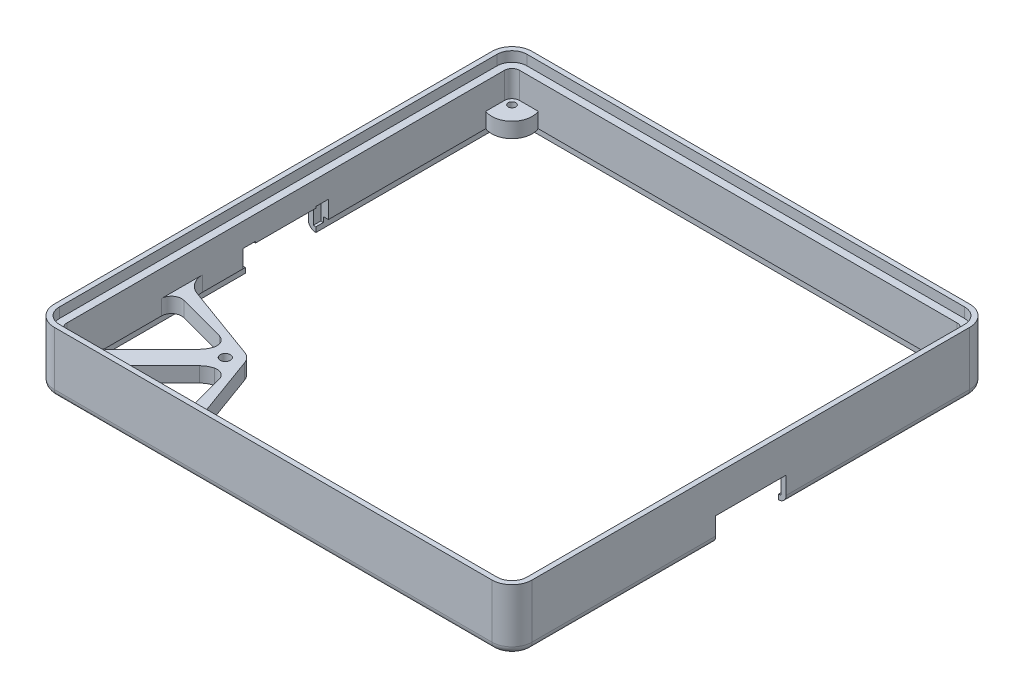
SolidWorks part; units mm, degrees
ref_plane "Front Plane" through (0, 0, 0) normal (0, 0, 1) x (1, 0, 0)
ref_plane "Top Plane" through (0, 0, 0) normal (0, 1, 0) x (1, 0, 0)
ref_plane "Right Plane" through (0, 0, 0) normal (1, 0, 0) x (0, 0, -1)
sketch "Sketch2" plane through (0, 0, 0) normal (0, 1, 0) x (1, 0, 0)
  line L1 (-43.5, -47.5) -> (43.5, -47.5)
  line L2 (-47.5, -43.5) -> (-47.5, 43.5)
  line L3 (-43.5, 47.5) -> (43.5, 47.5)
  line L4 (47.5, -43.5) -> (47.5, 43.5)
  line L5 (-43.5, -43.5) -> (43.5, 43.5) construction
  line L6 (-43.5, 43.5) -> (43.5, -43.5) construction
  arc A0 (-43.5, -47.5) -> (-47.5, -43.5) centre (-43.5, -43.5) cw
  arc A1 (43.5, -47.5) -> (47.5, -43.5) centre (43.5, -43.5) ccw
  arc A2 (43.5, 47.5) -> (47.5, 43.5) centre (43.5, 43.5) cw
  arc A3 (-47.5, 43.5) -> (-43.5, 47.5) centre (-43.5, 43.5) cw
  point P0 (0, 0)
  dimension "D1" = 4
  dimension "D2" = 95
sketch "Sketch3" plane through (0, 0, 0) normal (0, 0, 1) x (1, 0, 0)
  line L0 (0, 0) -> (0, -1.6)
  line L1 (-43.5, 0) -> (43.5, 0) construction
  line L2 (0, -1.6) -> (0, -8.5)
  line L3 (0, -8.5) -> (0, -10)
  dimension "D1" = 1.6
  dimension "D2" = 10
  dimension "D3" = 1.5
extrude "Boss-Extrude1" add sketch "Sketch2" against normal up to vertex (10 mm away) and the other way blind 2.2 up to point (0, -10, 0)
shell "Shell1" thickness 2.5 removed face at (0, -10, 0) removed face at (0, 2.2, 0)
sketch "Sketch4" plane through (0, 0, 0) normal (0, 1, 0) x (1, 0, 0)
  line L19 (-46.5, 43.5) -> (-46.5, -43.5)
  line L20 (-43.5, -46.5) -> (43.5, -46.5)
  line L21 (46.5, -43.5) -> (46.5, 43.5)
  line L22 (43.5, 46.5) -> (-43.5, 46.5)
  line L23 (-46.5, 43.5) -> (-46.5, -43.5)
  line L24 (-43.5, -46.5) -> (43.5, -46.5)
  line L25 (46.5, -43.5) -> (46.5, 43.5)
  line L26 (43.5, 46.5) -> (-43.5, 46.5)
  arc A16 (-46.5, -43.5) -> (-43.5, -46.5) centre (-43.5, -43.5) ccw
  arc A17 (43.5, -46.5) -> (46.5, -43.5) centre (43.5, -43.5) ccw
  arc A18 (46.5, 43.5) -> (43.5, 46.5) centre (43.5, 43.5) ccw
  arc A19 (-43.5, 46.5) -> (-46.5, 43.5) centre (-43.5, 43.5) ccw
  arc A20 (-46.5, -43.5) -> (-43.5, -46.5) centre (-43.5, -43.5) ccw
  arc A21 (43.5, -46.5) -> (46.5, -43.5) centre (43.5, -43.5) ccw
  arc A22 (46.5, 43.5) -> (43.5, 46.5) centre (43.5, 43.5) ccw
  arc A23 (-43.5, 46.5) -> (-46.5, 43.5) centre (-43.5, 43.5) ccw
  dimension "D1" = 1
extrude "Topplate cutout" cut sketch "Sketch4" along normal through all from offset 0.2
fillet "Fillet1" radius 1.5 8 edges at (-46.3284, -10, 46.3284) (-47.5, -10, 0) (-46.3284, -10, -46.3284) (0, -10, -47.5) (46.3284, -10, -46.3284) (47.5, -10, 0) (46.3284, -10, 46.3284) (0, -10, 47.5)
sketch "Sketch5" plane through (0, 0, 0) normal (1, 0, 0) x (0, 0, -1)
  line L0 (-8.5, -4.5) -> (-6, -4.5)
  line L1 (-7, -5) -> (7, -5)
  line L2 (-7, -5) -> (-7, -10)
  line L3 (-7, -10) -> (7, -10)
  line L4 (7, -5) -> (7, -10)
  line L5 (0, -8.5) -> (0, -10) construction
  line L6 (0, -8.5) -> (0, -10) construction
  line L7 (-6, -4.5) -> (-6, -4.8)
  line L8 (-6, -4.8) -> (6, -4.8)
  line L9 (6, -4.8) -> (6, -4.5)
  line L10 (6, -4.5) -> (8.5, -4.5)
  line L11 (-7, -9) -> (-8.5, -9)
  line L13 (-8.5, -9) -> (-8.5, -4.5)
  line L14 (8.5, -4.5) -> (8.5, -9)
  line L15 (8.5, -9) -> (7, -9)
  dimension "D1" = 14
  dimension "D2" = 5
  dimension "D3" = 1
  dimension "D4" = 17
  dimension "D5" = 12
  dimension "D6" = 0.2
  dimension "D7" = 0.5
extrude "connector cutout" cut sketch "Sketch5" against normal through all both and the other way through all contours L4 L1 L2 L3 region at (0, -7.5, 0)
ref_plane "Plane1" through (0, -10, 0) normal (0, 1, 0) x (1, 0, 0)
sketch "Sketch6" plane through (0, -10, 0) normal (0, 1, 0) x (1, 0, 0)
  line L0 (-41, 0) -> (0, 0) construction
  line L1 (-43.5, -43.5) -> (43.5, 43.5) construction
  line L2 (-46, -7) -> (-46, -43.5)
  line L3 (0, 0) -> (0, -32.2074) construction
  line L4 (-46, 7) -> (-41, 7)
  line L5 (-41, 7) -> (-41, -7)
  line L6 (-41, -7) -> (-46, -7)
  line L7 (41, -7) -> (46, -7)
  line L8 (-43.5, -46) -> (43.5, -46)
  line L9 (46, -43.5) -> (46, 43.5)
  line L10 (43.5, 46) -> (-43.5, 46)
  line L11 (-46, 43.5) -> (-46, -43.5)
  line L12 (-43.5, -46) -> (43.5, -46)
  line L13 (46, -43.5) -> (46, -7)
  line L14 (43.5, 46) -> (-43.5, 46)
  line L15 (-46, 43.5) -> (-46, 7)
  line L16 (41, 7) -> (41, -7)
  line L17 (46, 7) -> (41, 7)
  line L18 (46, 7) -> (46, 43.5)
  arc A8 (43.5, -46) -> (46, -43.5) centre (43.5, -43.5) ccw
  arc A9 (46, 43.5) -> (43.5, 46) centre (43.5, 43.5) ccw
  arc A10 (-43.5, 46) -> (-46, 43.5) centre (-43.5, 43.5) ccw
  arc A11 (-46, -43.5) -> (-43.5, -46) centre (-43.5, -43.5) ccw
  arc A12 (43.5, -46) -> (46, -43.5) centre (43.5, -43.5) ccw
  arc A13 (46, 43.5) -> (43.5, 46) centre (43.5, 43.5) ccw
  arc A14 (-43.5, 46) -> (-46, 43.5) centre (-43.5, 43.5) ccw
  arc A15 (-46, -43.5) -> (-43.5, -46) centre (-43.5, -43.5) ccw
  dimension "D2" = 14
  dimension "D3" = 5
  dimension "D1" = 1.5
extrude "Cut-Extrude1" cut sketch "Sketch6" along normal blind 2 contours L2 A15 L12 A12 L13 L7 L16 L17 L18 A13 L14 A14 L15 L4 L5 L6 | L12 A12 L13 L7 L16 L17 L18 A13 L14 A14 L15 L4 L5 L6 L2 A15 region at (0, -10, 0)
extrude "Cut-Extrude2" cut sketch "Sketch5<3>" along normal offset from surface 1 and the other way offset from surface 1 contours L15 L14 L10 L9 L8 L7 L0 L13 L11 L2 L1 L4 region at (0, -4.6759, 7.25) up to face at (47.5, -4.95, 0) other way up to face at (-47.5, -4.95, 0)
sketch "Sketch5<3>" plane through (0, 0, 0) normal (1, 0, 0) x (0, 0, -1) same geometry as "Sketch5"
sketch "Sketch8" plane through (0, -8, 0) normal (0, -1, 0) x (1, 0, 0)
  line L0 (-43.5, 43.5) -> (43.5, -43.5) construction
  line L1 (-43.5, -43.5) -> (43.5, 43.5) construction
  line L2 (-25.6809, 27.4739) -> (-20.2599, 42.3681)
  line L3 (-43.5, 45) -> (43.5, 45) construction
  line L5 (-39.0377, 41.8662) -> (-29.6353, 32.4637)
  line L6 (-25.3588, 32.8339) -> (-22.7735, 42.4824)
  line L8 (-43.5, 43.5) -> (43.5, -43.5) construction
  line L9 (-16.5011, 45) -> (-24.7053, 45)
  line L10 (-37.5209, 45) -> (-39.7919, 45)
  line L11 (-27.4739, 25.6809) -> (-42.3681, 20.2599)
  line L12 (-45, 16.5011) -> (-45, 24.7053)
  line L13 (-32.8339, 25.3588) -> (-42.4824, 22.7735)
  line L14 (-41.8662, 39.0377) -> (-32.4637, 29.6353)
  line L15 (-45, 37.5209) -> (-45, 39.7919)
  circle A0 centre (-43.5, 43.5) radius 4
  circle A1 centre (43.5, 43.5) radius 4
  circle A2 centre (43.5, -43.5) radius 4
  circle A3 centre (-43.5, -43.5) radius 4
  circle A4 centre (-43.5, 43.5) radius 0.75
  circle A5 centre (43.5, 43.5) radius 0.75
  circle A6 centre (-43.5, -43.5) radius 0.75
  circle A7 centre (43.5, -43.5) radius 0.75
  circle A8 centre (-28.5, 28.5) radius 1
  circle A9 centre (28.5, 28.5) radius 1
  circle A10 centre (-28.5, -28.5) radius 1
  circle A11 centre (28.5, -28.5) radius 1
  circle A12 centre (-28.5, 28.5) radius 3
  circle A13 centre (28.5, 28.5) radius 3
  circle A14 centre (28.5, -28.5) radius 3
  circle A15 centre (-28.5, -28.5) radius 3
  arc A16 (-20.2599, 42.3681) -> (-16.5011, 45) centre (-16.5011, 41) cw
  arc A17 (-39.5139, 43.1667) -> (-37.5209, 45) centre (-37.5209, 43) cw
  arc A18 (-39.5139, 43.1667) -> (-39.0377, 41.8662) centre (-37.8744, 43.0296) ccw
  arc A19 (-29.6353, 32.4637) -> (-27.7744, 31.4109) centre (-26.8069, 35.2922) ccw
  arc A20 (-27.7744, 31.4109) -> (-25.3588, 32.8339) centre (-27.2906, 33.3515) ccw
  arc A21 (-22.7735, 42.4824) -> (-24.7053, 45) centre (-24.7053, 43) ccw
  arc A22 (-42.3681, 20.2599) -> (-45, 16.5011) centre (-41, 16.5011) ccw
  arc A23 (-42.4824, 22.7735) -> (-45, 24.7053) centre (-43, 24.7053) cw
  arc A24 (-31.4109, 27.7744) -> (-32.8339, 25.3588) centre (-33.3515, 27.2906) cw
  arc A25 (-32.4637, 29.6353) -> (-31.4109, 27.7744) centre (-35.2922, 26.8069) cw
  arc A26 (-43.1667, 39.5139) -> (-41.8662, 39.0377) centre (-43.0296, 37.8744) cw
  arc A27 (-43.1667, 39.5139) -> (-45, 37.5209) centre (-43, 37.5209) ccw
  line M3 (45, -8.5) -> (45, -43.5)
  arc M4 (45, -43.5) -> (43.5, -45) centre (43.5, -43.5) cw
  line M5 (43.5, -45) -> (-43.5, -45)
  arc M6 (-43.5, -45) -> (-45, -43.5) centre (-43.5, -43.5) cw
  line M7 (-45, -43.5) -> (-45, -8.5)
  dimension "D1" = 1.5
  dimension "D2" = 57
  dimension "D3" = 2
  dimension "D5" = 2
  dimension "D6" = 2
  dimension "D7" = 4
  dimension "D8" = 2
  dimension "D9" = 2
  dimension "D10" = 4
  dimension "D4" = 2
  dimension "D11" = 5
  dimension "D12" = 60
extrude "Boss-Extrude3" add sketch "Sketch8" against normal blind 3 contours A0 A4 | A1 A5 | A2 A7 M3 M5 M4 | A3 A6 M5 M7 M6 region at (-44.0827, -8, 39.6571) region at (39.6131, -8, 43.5) region at (-42.3752, -8, -42.3752) region at (42.3752, -8, -42.3752)
extrude "Boss-Extrude6" add sketch "Sketch8<4>" against normal blind 3 contours L8 A0 A26 L14 A25 A12 | A0 L8 A12 A19 L5 A18 | A21 L6 A20 A12 L2 A16 L9 | A12 A24 L13 A23 L12 A22 L11 | L8 A12 A8 | A12 L8 A8 region at (-22.832, -8, 38.3817) region at (-27.5247, -8, 29.4753) region at (-29.4753, -8, 27.5247) region at (-34.8857, -8, 36.3342) region at (-38.3817, -8, 22.832) region at (-36.3342, -8, 34.8857)
sketch "Sketch8<4>" plane through (0, -8, 0) normal (0, -1, 0) x (1, 0, 0) same geometry as "Sketch8"
